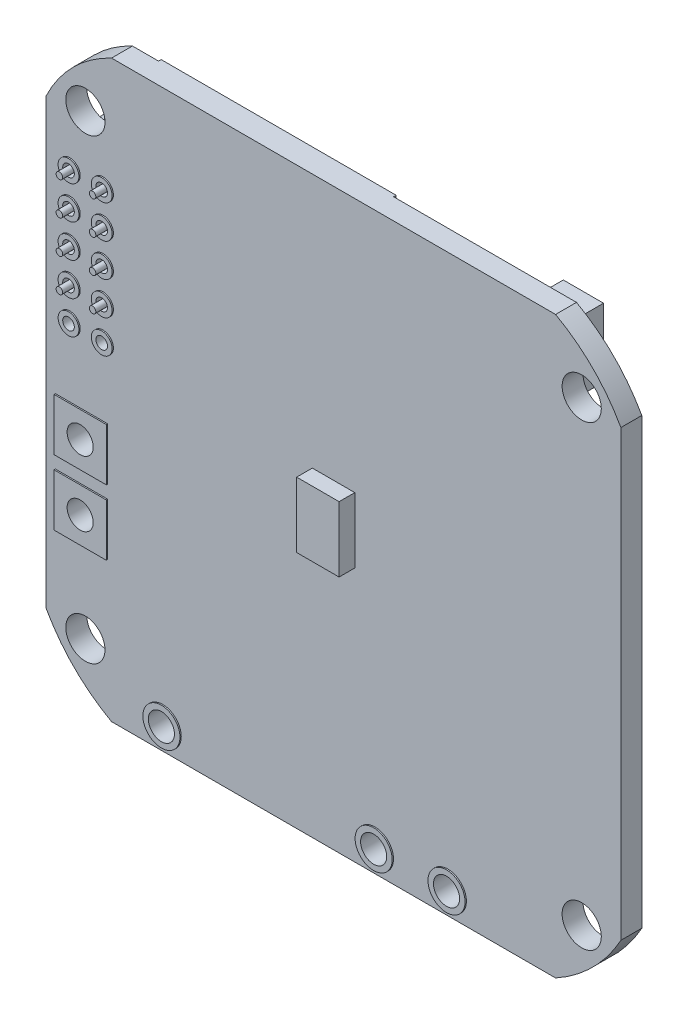
SolidWorks part; units mm, degrees
material "6061-T6 (SS)"
ref_plane "Alzado" through (0, 0, 0) normal (0, 0, 1) x (1, 0, 0)
ref_plane "Planta" through (0, 0, 0) normal (0, 1, 0) x (1, 0, 0)
ref_plane "Vista lateral" through (0, 0, 0) normal (1, 0, 0) x (0, 0, -1)
sketch "Croquis1" plane through (0, 0, 0) normal (0, 0, 1) x (1, 0, 0)
  line L0 (-22, 17) -> (-22, -17)
  line L1 (0, 0) -> (0, -6.2515) construction
  line L2 (22, 17) -> (22, -17)
  line L3 (-17, -22) -> (17, -22)
  line L4 (0, 0) -> (8.2976, 0) construction
  line L5 (-17, 22) -> (17, 22)
  arc A0 (-17, 22) -> (-22, 17) centre (-12.5089, 12.5089) ccw
  arc A2 (17, -22) -> (22, -17) centre (10.8379, -10.8379) ccw
  arc A3 (-22, -17) -> (-17, -22) centre (-10.8379, -10.8379) ccw
  arc A7 (22, 17) -> (17, 22) centre (10.8379, 10.8379) ccw
  point P0 (0, 0)
  point P4 (-22, 0)
  point P13 (0, -22)
  dimension "D3" = 21
  dimension "D4" = 34
  dimension "D1" = 34
  dimension "D2" = 22
  dimension "D5" = 22
extrude "Saliente-Extruir1" add sketch "Croquis1" along normal mid plane 1.6
sketch "Croquis2" plane through (0, 0, 0.8) normal (0, 0, 1) x (1, 0, 0)
  line L1 (19, -17.5) -> (-19, -17.5) construction
  line L2 (19, -17.5) -> (19, 17.5) construction
  line L3 (19, 17.5) -> (-19, 17.5) construction
  line L4 (-19, -17.5) -> (-19, 17.5) construction
  line L5 (19, -17.5) -> (-19, 17.5) construction
  line L6 (19, 17.5) -> (-19, -17.5) construction
  circle A0 centre (-19, 17.5) radius 1.5
  circle A1 centre (19, 17.5) radius 1.5
  circle A2 centre (19, -17.5) radius 1.5
  circle A3 centre (-19, -17.5) radius 1.5
  point P0 (0, 0)
  dimension "D1" = 3
  dimension "D2" = 38
  dimension "D3" = 35
extrude "Cortar-Extruir1" cut sketch "Croquis2" against normal through all
sketch "Croquis3" plane through (0, 0, 0.8) normal (0, 0, 1) x (1, 0, 0)
  line L1 (-1.625, 2.5) -> (1.625, 2.5)
  line L2 (-1.625, 2.5) -> (-1.625, -2.5)
  line L3 (-1.625, -2.5) -> (1.625, -2.5)
  line L4 (1.625, 2.5) -> (1.625, -2.5)
  line L5 (-1.625, 2.5) -> (1.625, -2.5) construction
  line L6 (-1.625, -2.5) -> (1.625, 2.5) construction
  point P0 (0, 0)
  dimension "D1" = 5
  dimension "D2" = 3.25
extrude "Saliente-Extruir2" add sketch "Croquis3" along normal blind 1.2
sketch "Croquis4" plane through (0, 0, -0.8) normal (0, 0, -1) x (-1, 0, 0)
  line L0 (22, 17) -> (22, -17) construction
  line L1 (-17, 22) -> (17, 22) construction
  circle A0 centre (17.653, 13) radius 0.445
  circle A1 centre (20.193, 13) radius 0.445
  circle A2 centre (20.193, 10.46) radius 0.445
  circle A3 centre (20.193, 7.92) radius 0.445
  circle A4 centre (20.193, 5.38) radius 0.445
  circle A5 centre (20.193, 2.84) radius 0.445
  circle A6 centre (17.653, 10.46) radius 0.445
  circle A7 centre (17.653, 7.92) radius 0.445
  circle A8 centre (17.653, 5.38) radius 0.445
  circle A9 centre (17.653, 2.84) radius 0.445
  dimension "D1" = 0.89
  dimension "D3" = 1.807
  dimension "D4" = 9
  dimension "D5" = 2.54
  dimension "D2" = 5
extrude "Cortar-Extruir2" cut sketch "Croquis4" against normal through all
sketch "Croquis5" plane through (0, 0, 0) normal (0, 0, 1) x (1, 0, 0)
  line L0 (-17, -22) -> (17, -22) construction
  line L1 (-17.3, -2.4) -> (-21.3, -2.4)
  line L2 (-17.3, -2.4) -> (-17.3, -6.4)
  line L3 (-17.3, -6.4) -> (-21.3, -6.4)
  line L4 (-21.3, -2.4) -> (-21.3, -6.4)
  line L5 (-17.3, -2.4) -> (-21.3, -6.4) construction
  line L6 (-17.3, -6.4) -> (-21.3, -2.4) construction
  line L7 (-17.3, -7.4) -> (-21.3, -7.4)
  line L8 (-17.3, -7.4) -> (-17.3, -11.4)
  line L9 (-17.3, -11.4) -> (-21.3, -11.4)
  line L10 (-21.3, -7.4) -> (-21.3, -11.4)
  line L11 (-17.3, -7.4) -> (-21.3, -11.4) construction
  line L12 (-17.3, -11.4) -> (-21.3, -7.4) construction
  line L13 (-22, 17) -> (-22, -17) construction
  circle A0 centre (-17.653, 2.84) radius 0.7974
  circle A1 centre (-20.193, 2.84) radius 0.7974
  circle A2 centre (-20.193, 5.38) radius 0.7974
  circle A3 centre (-17.653, 5.38) radius 0.7974
  circle A4 centre (-17.653, 7.92) radius 0.7974
  circle A5 centre (-17.653, 10.46) radius 0.7974
  circle A6 centre (-20.193, 7.92) radius 0.7974
  circle A7 centre (-20.193, 10.46) radius 0.7974
  circle A8 centre (-17.653, 13) radius 0.7974
  circle A9 centre (-20.193, 13) radius 0.7974
  circle A10 centre (-17.653, 13) radius 0.445
  circle A11 centre (-20.193, 13) radius 0.445
  circle A12 centre (-20.193, 10.46) radius 0.445
  circle A13 centre (-17.653, 10.46) radius 0.445
  circle A14 centre (-17.653, 7.92) radius 0.445
  circle A15 centre (-20.193, 7.92) radius 0.445
  circle A16 centre (-20.193, 5.38) radius 0.445
  circle A17 centre (-17.653, 5.38) radius 0.445
  circle A18 centre (-17.653, 2.84) radius 0.445
  circle A19 centre (-20.193, 2.84) radius 0.445
  point P0 (-19.3, -4.4)
  point P5 (-19.3, -9.4)
  dimension "D1" = 4
  dimension "D2" = 4
  dimension "D3" = 5
  dimension "D4" = 4
  dimension "D5" = 4
  dimension "D6" = 12.6
  dimension "D7" = 2.7
extrude "Saliente-Extruir3" add sketch "Croquis5" along normal mid plane 1.8
sketch "Croquis6" plane through (0, 0, -0.9) normal (0, 0, -1) x (-1, 0, 0)
  line L0 (21.3, -2.4) -> (21.3, -6.4) construction
  line L1 (21.3, -7.4) -> (21.3, -11.4) construction
  circle A0 centre (19.3, -4.4) radius 1
  circle A1 centre (19.3, -9.4) radius 1
  point P6 (21.3, -4.4)
  point P9 (21.3, -9.4)
  dimension "D1" = 2
extrude "Cortar-Extruir3" cut sketch "Croquis6" against normal through all both and the other way through all
sketch "Croquis7" plane through (0, 0, -0.8) normal (0, 0, -1) x (-1, 0, 0)
  line L0 (17, -22) -> (-17, -22) construction
  line L1 (22, 17) -> (22, -17) construction
  circle A0 centre (-8.75, -20.32) radius 1
  circle A1 centre (-3.17, -20.32) radius 1
  circle A2 centre (13.08, -20.32) radius 1
  dimension "D1" = 2
  dimension "D2" = 1.68
  dimension "D3" = 5.58
  dimension "D4" = 16.25
  dimension "D5" = 8.92
extrude "Cortar-Extruir4" cut sketch "Croquis7" against normal blind 10
sketch "Croquis8" plane through (0, 0, -0.8) normal (0, 0, -1) x (-1, 0, 0)
  line L0 (-22, -17) -> (-22, 17) construction
  line L1 (-20.5, 13.45) -> (-17.5, 13.45)
  line L2 (-20.5, 13.45) -> (-20.5, 10.95)
  line L3 (-20.5, 10.95) -> (-17.5, 10.95)
  line L4 (-17.5, 13.45) -> (-17.5, 10.95)
  line L5 (-20.5, 10.275) -> (-17.5, 10.275)
  line L6 (-20.5, 10.275) -> (-20.5, 7.775)
  line L7 (-20.5, 7.775) -> (-17.5, 7.775)
  line L8 (-17.5, 10.275) -> (-17.5, 7.775)
  line L10 (-17, 22) -> (17, 22) construction
  point P8 (-19, 7.775)
  point P11 (-20.5, 12.2)
  point P12 (-20.5, 9.025)
  point P15 (-17.5, 12.2)
  dimension "D1" = 3
  dimension "D2" = 3
  dimension "D3" = 2.5
  dimension "D4" = 3.175
  dimension "D5" = 9.8
extrude "Saliente-Extruir4" add sketch "Croquis8" along normal blind 1.2
sketch "Croquis9" plane through (0, 0, -2) normal (0, 0, -1) x (-1, 0, 0)
  line L0 (-17.5, 13.45) -> (-20.5, 13.45) construction
  line L1 (-17.5, 7.775) -> (-17.5, 10.275) construction
  line L2 (-17.5, 10.95) -> (-17.5, 13.45) construction
  circle A0 centre (-19, 12.2) radius 0.75
  circle A1 centre (-19, 9.025) radius 0.75
  point P7 (-19, 13.45)
  point P10 (-17.5, 9.025)
  point P14 (-17.5, 12.2)
  dimension "D1" = 1.5
extrude "Saliente-Extruir5" add sketch "Croquis9" along normal blind 0.8
sketch "Croquis10" plane through (0, 0, -0.8) normal (0, 0, -1) x (-1, 0, 0)
  line L0 (-22, -17) -> (-22, 17) construction
  line L1 (-16, -14.25) -> (-11, -14.25)
  line L2 (-16, -14.25) -> (-16, -19.25)
  line L3 (-16, -19.25) -> (-11, -19.25)
  line L4 (-11, -14.25) -> (-11, -19.25)
  line L5 (17, -22) -> (-17, -22) construction
  line L6 (11.25, -12.2) -> (16.25, -12.2)
  line L7 (11.25, -12.2) -> (11.25, -17.2)
  line L8 (11.25, -17.2) -> (16.25, -17.2)
  line L9 (16.25, -12.2) -> (16.25, -17.2)
  line L10 (5.8877, -14.25) -> (10.8877, -14.25)
  line L11 (5.8877, -14.25) -> (5.8877, -19.25)
  line L12 (5.8877, -19.25) -> (10.8877, -19.25)
  line L13 (10.8877, -14.25) -> (10.8877, -19.25)
  line L14 (0.4343, -14.25) -> (5.4343, -14.25)
  line L15 (0.4343, -14.25) -> (0.4343, -19.25)
  line L16 (0.4343, -19.25) -> (5.4343, -19.25)
  line L17 (5.4343, -14.25) -> (5.4343, -19.25)
  line L18 (22, 17) -> (22, -17) construction
  line L19 (-4.9483, -12.2) -> (0.0517, -12.2)
  line L20 (-4.9483, -12.2) -> (-4.9483, -17.2)
  line L21 (-4.9483, -17.2) -> (0.0517, -17.2)
  line L22 (0.0517, -12.2) -> (0.0517, -17.2)
  line L23 (-10.5433, -12.2) -> (-5.5433, -12.2)
  line L24 (-10.5433, -12.2) -> (-10.5433, -17.2)
  line L25 (-10.5433, -17.2) -> (-5.5433, -17.2)
  line L26 (-5.5433, -12.2) -> (-5.5433, -17.2)
  dimension "D1" = 5
  dimension "D2" = 5
  dimension "D3" = 6
  dimension "D4" = 2.75
  dimension "D5" = 5
  dimension "D6" = 5
  dimension "D7" = 5
  dimension "D8" = 5
  dimension "D9" = 5
  dimension "D10" = 5
  dimension "D11" = 5.75
  dimension "D12" = 4.8
  dimension "D13" = 5
  dimension "D14" = 5
  dimension "D15" = 5
  dimension "D16" = 5
extrude "Saliente-Extruir6" add sketch "Croquis10" along normal blind 0.9
sketch "Croquis11" plane through (0, 0, -0.8) normal (0, 0, -1) x (-1, 0, 0)
  line L0 (-13.6529, -19.5225) -> (-10.4593, -19.5225)
  line L1 (-10.4593, -19.5225) -> (-9.8124, -18.8756)
  line L2 (-9.8124, -18.8756) -> (-7.529, -18.8756)
  line L3 (-7.529, -18.8756) -> (-7.1476, -19.257)
  line L4 (-7.1476, -19.257) -> (-7.1476, -21.3437)
  line L5 (-7.1476, -21.3437) -> (-7.529, -21.7251)
  line L6 (-7.529, -21.7251) -> (-13.8301, -21.7251)
  line L7 (-13.8301, -21.7251) -> (-14.1414, -21.4138)
  line L8 (-14.1414, -21.4138) -> (-14.1414, -20.011)
  line L9 (-14.1414, -20.011) -> (-13.6529, -19.5225)
  line L10 (8.1723, -19.5225) -> (11.1983, -19.5225)
  line L11 (11.1983, -19.5225) -> (12.0225, -18.6983)
  line L12 (12.0225, -18.6983) -> (14.2962, -18.6983)
  line L13 (14.2962, -18.6983) -> (14.7785, -19.1806)
  line L14 (14.7785, -19.1806) -> (14.7785, -21.2429)
  line L15 (14.7785, -21.2429) -> (14.2962, -21.7251)
  line L16 (14.2962, -21.7251) -> (7.9951, -21.7251)
  line L17 (7.9951, -21.7251) -> (7.6839, -21.4138)
  line L18 (7.6839, -21.4138) -> (7.6839, -20.011)
  line L19 (7.6839, -20.011) -> (8.1723, -19.5225)
  line L20 (2.2631, -20.011) -> (1.7746, -19.5225)
  line L21 (2.2631, -21.4138) -> (2.2631, -20.011)
  line L22 (1.9518, -21.7251) -> (2.2631, -21.4138)
  line L23 (-4.3493, -21.7251) -> (1.9518, -21.7251)
  line L24 (-4.7307, -21.3437) -> (-4.3493, -21.7251)
  line L25 (-4.7307, -19.257) -> (-4.7307, -21.3437)
  line L26 (-4.3493, -18.8756) -> (-4.7307, -19.257)
  line L27 (-2.0659, -18.8756) -> (-4.3493, -18.8756)
  line L28 (-1.4189, -19.5225) -> (-2.0659, -18.8756)
  line L29 (1.7746, -19.5225) -> (-1.4189, -19.5225)
  line L30 (-5.9391, -18.0693) -> (-5.9391, -23.1735) construction
  circle A0 centre (-8.75, -20.32) radius 1
  circle A1 centre (-3.17, -20.32) radius 1
  circle A2 centre (13.08, -20.32) radius 1
extrude "Saliente-Extruir7" add sketch "Croquis11" along normal blind 0.1
sketch "Croquis12" plane through (0, 0, -0.8) normal (0, 0, -1) x (-1, 0, 0)
  line L0 (-19.5752, -2.7898) -> (-13.4845, -8.8805)
  line L1 (-19.5752, -2.7898) -> (-13.4845, 3.301)
  line L2 (-13.4845, -8.8805) -> (-7.3937, -2.7898)
  line L3 (-13.4845, 3.301) -> (-7.3937, -2.7898)
  line L4 (17, -22) -> (-17, -22) construction
  dimension "D1" = 45
extrude "Saliente-Extruir8" add sketch "Croquis12" along normal blind 0.75
sketch "Croquis13" plane through (0, 0, -0.8) normal (0, 0, -1) x (-1, 0, 0)
  line L1 (-16.4217, 20.3319) -> (-13.3413, 20.3319)
  line L2 (-16.4217, 20.3319) -> (-16.4217, 15.0982)
  line L3 (-16.4217, 15.0982) -> (-13.3413, 15.0982)
  line L4 (-13.3413, 20.3319) -> (-13.3413, 15.0982)
extrude "Saliente-Extruir9" add sketch "Croquis13" along normal blind 2.65
sketch "Croquis14" plane through (0, 0, -0.8) normal (0, 0, -1) x (-1, 0, 0)
  line L1 (-12.0511, 17.4084) -> (-8.2311, 17.4084)
  line L2 (-12.0511, 17.4084) -> (-12.0511, 13.5884)
  line L3 (-12.0511, 13.5884) -> (-8.2311, 13.5884)
  line L4 (-8.2311, 17.4084) -> (-8.2311, 13.5884)
  dimension "D1" = 3.82
extrude "Saliente-Extruir10" add sketch "Croquis14" along normal blind 3
sketch "Croquis30" plane through (0, 0, 0.8) normal (0, 0, 1) x (1, 0, 0)
  circle A0 centre (-13.08, -20.32) radius 1.4199
  circle A1 centre (8.75, -20.32) radius 1.4199
  circle A2 centre (3.17, -20.32) radius 1.4199
  circle A3 centre (-13.08, -20.32) radius 1
  circle A4 centre (3.17, -20.32) radius 1
  circle A5 centre (8.75, -20.32) radius 1
extrude "Saliente-Extruir17" add sketch "Croquis30" along normal blind 0.1
sketch "Croquis29" plane through (0, 0, -0.8) normal (0, 0, -1) x (-1, 0, 0)
  line L0 (-17, 22) -> (17, 22) construction
  line L1 (10.5, 1.5) -> (14, 1.5)
  line L2 (10.5, 1.5) -> (10.5, 0)
  line L3 (10.5, 0) -> (14, 0)
  line L4 (14, 1.5) -> (14, 0)
  line L5 (10.5, -0.65) -> (14, -0.65)
  line L6 (10.5, -0.65) -> (10.5, -2.15)
  line L7 (10.5, -2.15) -> (14, -2.15)
  line L8 (14, -0.65) -> (14, -2.15)
  line L9 (2.75, 1.5) -> (6.25, 1.5)
  line L10 (2.75, 1.5) -> (2.75, 0)
  line L11 (2.75, 0) -> (6.25, 0)
  line L12 (6.25, 1.5) -> (6.25, 0)
  line L13 (22, 17) -> (22, -17) construction
  dimension "D1" = 3.5
  dimension "D2" = 1.5
  dimension "D3" = 0.65
  dimension "D4" = 3.5
  dimension "D5" = 20.5
  dimension "D6" = 11.5
  dimension "D7" = 7.75
extrude "Saliente-Extruir16" add sketch "Croquis29" along normal blind 0.5
sketch "Croquis31" plane through (0, 0, -0.8) normal (0, 0, -1) x (-1, 0, 0)
  line L0 (-17, 22) -> (17, 22) construction
  line L1 (-3, 22) -> (15, 22)
  line L2 (-3, 22) -> (-3, 2.65)
  line L3 (-3, 2.65) -> (15, 2.65)
  line L4 (15, 22) -> (15, 2.65)
  line L5 (22, 17) -> (22, -17) construction
  dimension "D1" = 19.35
  dimension "D2" = 18
  dimension "D3" = 7
extrude "Boss-Extrude1" add sketch "Croquis31" along normal blind 0.2
chamfer "Chaflán1" distance 1 angle 45 4 edges at (12.0511, 17.4084, -2.3) (8.2311, 17.4084, -2.3) (12.0511, 13.5884, -2.3) (8.2311, 13.5884, -2.3)
sketch "Croquis32" plane through (0, 0, -0.9) normal (0, 0, -1) x (-1, 0, 0)
  circle A0 centre (17.653, 13) radius 0.65
  circle A1 centre (20.193, 13) radius 0.65
  circle A2 centre (20.193, 10.46) radius 0.65
  circle A3 centre (17.653, 10.46) radius 0.65
  circle A4 centre (17.653, 7.92) radius 0.65
  circle A5 centre (20.193, 7.92) radius 0.65
  circle A6 centre (20.193, 5.38) radius 0.65
  circle A7 centre (17.653, 5.38) radius 0.65
  dimension "D1" = 1.3
extrude "Saliente-Extruir18" add sketch "Croquis32" along normal blind 1.6
sketch "Croquis33" plane through (0, 0, -0.9) normal (0, 0, 1) x (1, 0, 0)
  circle A0 centre (-20.193, 13) radius 0.25
  circle A1 centre (-17.653, 13) radius 0.25
  circle A2 centre (-17.653, 10.46) radius 0.25
  circle A3 centre (-20.193, 10.46) radius 0.25
  circle A4 centre (-20.193, 7.92) radius 0.25
  circle A5 centre (-17.653, 7.92) radius 0.25
  circle A6 centre (-17.653, 5.38) radius 0.25
  circle A7 centre (-20.193, 5.38) radius 0.25
  dimension "D1" = 0.5
extrude "Saliente-Extruir19" add sketch "Croquis33" along normal blind 2.5
sketch "Croquis34" plane through (0, 0, -2.5) normal (0, 0, -1) x (-1, 0, 0)
  line L0 (16.388, 14.1102) -> (16.388, 11.9202)
  line L1 (16.388, 11.9202) -> (16.8728, 11.735)
  line L2 (16.8728, 11.735) -> (18.4226, 11.735)
  line L3 (18.4226, 11.735) -> (18.918, 11.8898)
  line L4 (18.918, 11.8898) -> (18.918, 14.1102)
  line L5 (18.918, 14.1102) -> (18.4332, 14.265)
  line L6 (18.4332, 14.265) -> (16.8728, 14.265)
  line L7 (16.8728, 14.265) -> (16.388, 14.1102)
  line L8 (17.653, 13) -> (17.653, 14.4547) construction
  line L9 (17.653, 13) -> (15.9852, 13) construction
  line L10 (18.928, 14.1102) -> (18.928, 11.9202)
  line L11 (18.928, 11.9202) -> (19.4128, 11.735)
  line L12 (19.4128, 11.735) -> (20.9626, 11.735)
  line L13 (20.9626, 11.735) -> (21.458, 11.8898)
  line L14 (21.458, 11.8898) -> (21.458, 14.1102)
  line L15 (21.458, 14.1102) -> (20.9732, 14.265)
  line L16 (20.9732, 14.265) -> (19.4128, 14.265)
  line L17 (19.4128, 14.265) -> (18.928, 14.1102)
  line L18 (20.193, 13) -> (20.193, 14.4547) construction
  line L19 (20.193, 13) -> (18.5252, 13) construction
  line L20 (18.928, 11.5702) -> (18.928, 9.3802)
  line L21 (18.928, 9.3802) -> (19.4128, 9.195)
  line L22 (19.4128, 9.195) -> (20.9626, 9.195)
  line L23 (20.9626, 9.195) -> (21.458, 9.3498)
  line L24 (21.458, 9.3498) -> (21.458, 11.5702)
  line L25 (21.458, 11.5702) -> (20.9732, 11.725)
  line L26 (20.9732, 11.725) -> (19.4128, 11.725)
  line L27 (19.4128, 11.725) -> (18.928, 11.5702)
  line L28 (20.193, 10.46) -> (20.193, 11.9147) construction
  line L29 (20.193, 10.46) -> (18.5252, 10.46) construction
  line L30 (16.388, 11.5702) -> (16.388, 9.3802)
  line L31 (16.388, 9.3802) -> (16.8728, 9.195)
  line L32 (16.8728, 9.195) -> (18.4226, 9.195)
  line L33 (18.4226, 9.195) -> (18.918, 9.3498)
  line L34 (18.918, 9.3498) -> (18.918, 11.5702)
  line L35 (18.918, 11.5702) -> (18.4332, 11.725)
  line L36 (18.4332, 11.725) -> (16.8728, 11.725)
  line L37 (16.8728, 11.725) -> (16.388, 11.5702)
  line L38 (17.653, 10.46) -> (17.653, 11.9147) construction
  line L39 (17.653, 10.46) -> (15.9852, 10.46) construction
  line L40 (16.388, 9.0302) -> (16.388, 6.8402)
  line L41 (16.388, 6.8402) -> (16.8728, 6.655)
  line L42 (16.8728, 6.655) -> (18.4226, 6.655)
  line L43 (18.4226, 6.655) -> (18.918, 6.8098)
  line L44 (18.918, 6.8098) -> (18.918, 9.0302)
  line L45 (18.918, 9.0302) -> (18.4332, 9.185)
  line L46 (18.4332, 9.185) -> (16.8728, 9.185)
  line L47 (16.8728, 9.185) -> (16.388, 9.0302)
  line L48 (17.653, 7.92) -> (17.653, 9.3747) construction
  line L49 (17.653, 7.92) -> (15.9852, 7.92) construction
  line L50 (18.928, 9.0302) -> (18.928, 6.8402)
  line L51 (18.928, 6.8402) -> (19.4128, 6.655)
  line L52 (19.4128, 6.655) -> (20.9626, 6.655)
  line L53 (20.9626, 6.655) -> (21.458, 6.8098)
  line L54 (21.458, 6.8098) -> (21.458, 9.0302)
  line L55 (21.458, 9.0302) -> (20.9732, 9.185)
  line L56 (20.9732, 9.185) -> (19.4128, 9.185)
  line L57 (19.4128, 9.185) -> (18.928, 9.0302)
  line L58 (20.193, 7.92) -> (20.193, 9.3747) construction
  line L59 (20.193, 7.92) -> (18.5252, 7.92) construction
  line L60 (16.388, 6.4902) -> (16.388, 4.3002)
  line L61 (16.388, 4.3002) -> (16.8728, 4.115)
  line L62 (16.8728, 4.115) -> (18.4226, 4.115)
  line L63 (18.4226, 4.115) -> (18.918, 4.2698)
  line L64 (18.918, 4.2698) -> (18.918, 6.4902)
  line L65 (18.918, 6.4902) -> (18.4332, 6.645)
  line L66 (18.4332, 6.645) -> (16.8728, 6.645)
  line L67 (16.8728, 6.645) -> (16.388, 6.4902)
  line L68 (17.653, 5.38) -> (17.653, 6.8347) construction
  line L69 (17.653, 5.38) -> (15.9852, 5.38) construction
  line L70 (18.928, 6.4902) -> (18.928, 4.3002)
  line L71 (18.928, 4.3002) -> (19.4128, 4.115)
  line L72 (19.4128, 4.115) -> (20.9626, 4.115)
  line L73 (20.9626, 4.115) -> (21.458, 4.2698)
  line L74 (21.458, 4.2698) -> (21.458, 6.4902)
  line L75 (21.458, 6.4902) -> (20.9732, 6.645)
  line L76 (20.9732, 6.645) -> (19.4128, 6.645)
  line L77 (19.4128, 6.645) -> (18.928, 6.4902)
  line L78 (20.193, 5.38) -> (20.193, 6.8347) construction
  line L79 (20.193, 5.38) -> (18.5252, 5.38) construction
  circle A0 centre (17.653, 13) radius 0.65
  circle A1 centre (20.193, 13) radius 0.64
  circle A2 centre (20.193, 10.46) radius 0.6641
  circle A3 centre (17.653, 10.46) radius 0.65
  circle A4 centre (17.653, 7.92) radius 0.65
  circle A5 centre (20.193, 7.92) radius 0.65
  circle A6 centre (20.193, 5.38) radius 0.65
  circle A7 centre (17.653, 5.38) radius 0.65
  circle A8 centre (17.653, 10.46) radius 0.65 construction
  point P2 (17.653, 14.265)
  point P9 (18.918, 13)
  point P100 (20.193, 10.46)
  dimension "D1" = 2.53
  dimension "D2" = 2.53
  dimension "D3" = 2
  dimension "D4" = 4
extrude "Saliente-Extruir20" add sketch "Croquis34" along normal blind 3
